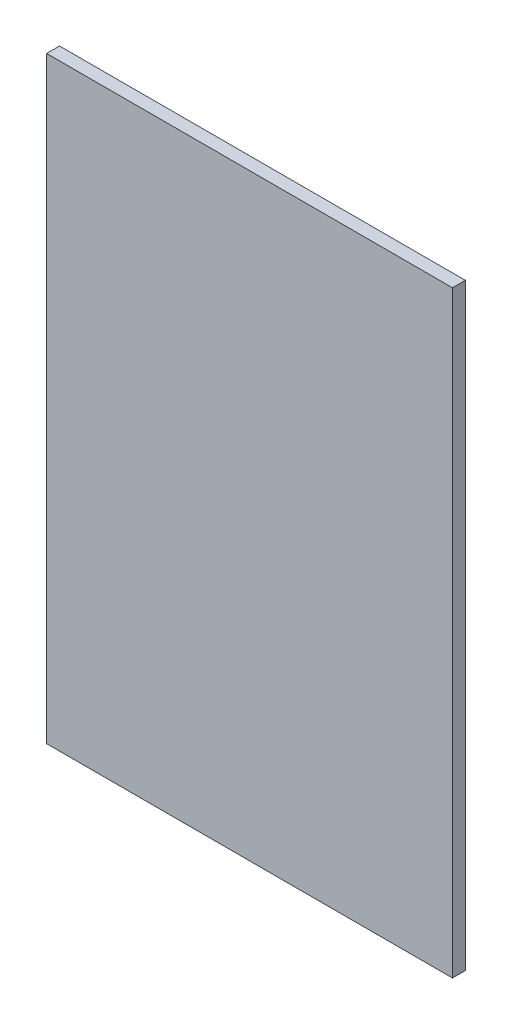
SolidWorks part; units mm, degrees
ref_plane "Front Plane" through (0, 0, 0) normal (0, 0, 1) x (1, 0, 0)
ref_plane "Top Plane" through (0, 0, 0) normal (0, 1, 0) x (1, 0, 0)
ref_plane "Right Plane" through (0, 0, 0) normal (1, 0, 0) x (0, 0, -1)
sketch "Sketch1" plane through (0, 0, 0) normal (0, 0, 1) x (1, 0, 0)
  line L0 (-50, 73.645) -> (-16.6667, 73.645)
  line L1 (-50, -73.645) -> (50, -73.645)
  line L2 (-50, -73.645) -> (-50, 73.645)
  line L3 (-50, 73.645) -> (50, 73.645) construction
  line L4 (50, -73.645) -> (50, 73.645)
  line L5 (-50, -73.645) -> (50, 73.645) construction
  line L6 (-50, 73.645) -> (50, -73.645) construction
  line L7 (-16.6667, 73.645) -> (16.6667, 73.645)
  line L8 (16.6667, 73.645) -> (50, 73.645)
  point P0 (0, 0)
  dimension "D1" = 100
  dimension "D2" = 147.29
extrude "Boss-Extrude1" add sketch "Sketch1" along normal blind 3.18
